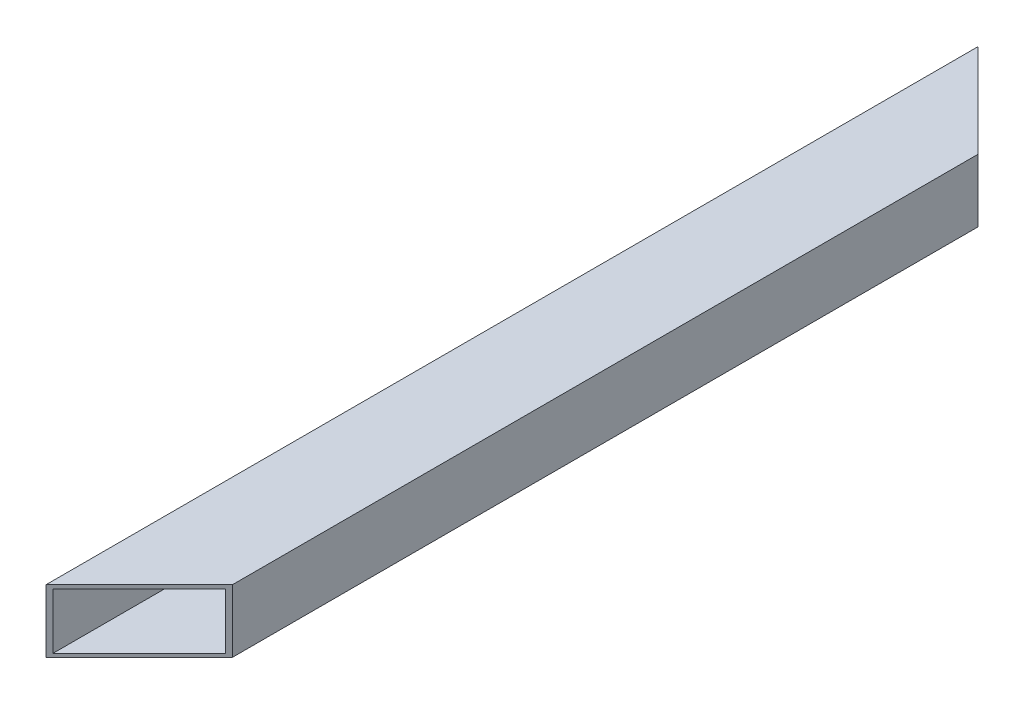
SolidWorks part; units mm, degrees
material "AISI 1020 Acier laminé à froid"
ref_plane "Plan de face" through (0, 0, 0) normal (0, 0, 1) x (1, 0, 0)
ref_plane "Plan de dessus" through (0, 0, 0) normal (0, 1, 0) x (1, 0, 0)
ref_plane "Plan de droite" through (0, 0, 0) normal (1, 0, 0) x (0, 0, -1)
sketch "Esquisse1" plane through (0, 0, 0) normal (0, 0, 1) x (1, 0, 0)
  line L1 (0, 0) -> (40, 0)
  line L2 (0, 0) -> (0, 27)
  line L3 (0, 27) -> (40, 27)
  line L4 (40, 0) -> (40, 27)
  line L5 (1.5, 25.5) -> (38.5, 25.5)
  line L6 (1.5, 25.5) -> (1.5, 1.5)
  line L7 (1.5, 1.5) -> (38.5, 1.5)
  line L8 (38.5, 25.5) -> (38.5, 1.5)
  dimension "D1" = 40
  dimension "D2" = 27
  dimension "D3" = 1.5
  dimension "D4" = 1.5
  dimension "D5" = 1.5
  dimension "D6" = 1.5
extrude "Boss.-Extru.1" add sketch "Esquisse1" along normal blind 400
sketch "Esquisse2" plane through (0, 0, 0) normal (0, 1, 0) x (1, 0, 0)
  line L0 (0, -400) -> (40, -360)
  line L1 (40, -400) -> (40, 0) construction
  line L2 (0, -400) -> (40, -400)
  line L3 (40, -400) -> (40, -360)
  dimension "D1" = 45
extrude "Enlèv. mat.-Extru.1" cut sketch "Esquisse2" along normal through all
sketch "Esquisse4" plane through (0, 0, 0) normal (0, 1, 0) x (1, 0, 0)
  line L0 (0, 0) -> (40, -40)
  line L1 (40, -360) -> (40, 0) construction
  line L2 (40, -40) -> (40, 0)
  line L3 (40, 0) -> (0, 0)
  dimension "D1" = 45
extrude "Enlèv. mat.-Extru.3" cut sketch "Esquisse4" along normal through all
